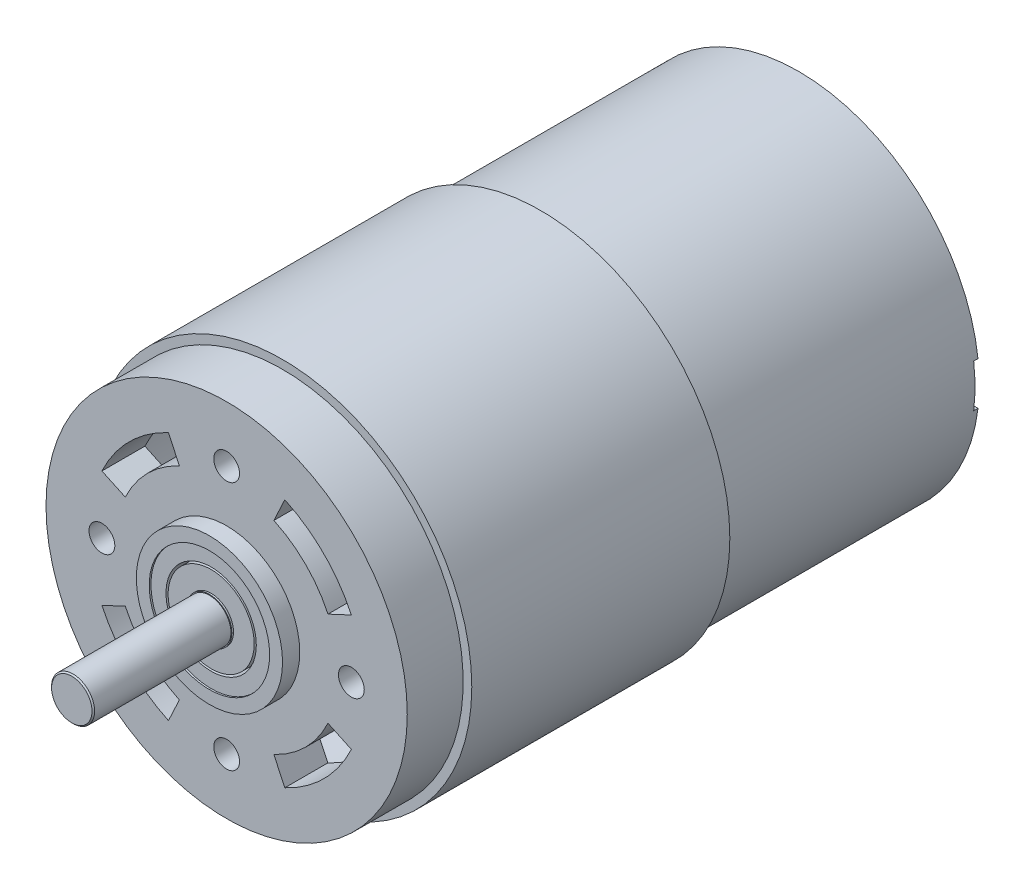
SolidWorks part; units mm, degrees
ref_plane "正面" through (0, 0, 0) normal (0, 0, 1) x (1, 0, 0)
ref_plane "平面" through (0, 0, 0) normal (0, 1, 0) x (1, 0, 0)
ref_plane "右側面" through (0, 0, 0) normal (1, 0, 0) x (0, 0, -1)
sketch "Sketch1" plane through (0, 0, 0) normal (0, 0, 1) x (1, 0, 0)
  circle A0 centre (0, 0) radius 21
  dimension "D1" = 42
extrude "Boss-Extrude1" add sketch "Sketch1" along normal blind 66.5
sketch "Sketch2" plane through (0, 0, 66.5) normal (0, 0, 1) x (1, 0, 0)
  circle A0 centre (0, 0) radius 8.5
  dimension "D1" = 17
extrude "Boss-Extrude2" add sketch "Sketch2" along normal blind 2
sketch "Sketch4" plane through (0, 0, 0) normal (0, 0, -1) x (-1, 0, 0)
  circle A0 centre (0, 0) radius 2.5
  dimension "D1" = 5
extrude "Boss-Extrude3" add sketch "Sketch4" against normal blind 92.5 from offset 8
chamfer "Chamfer1" distance 0.15 angle 45 2 edges at (-2.5, 0, 84.5) (-2.5, 0, -8)
sketch "Sketch5" plane through (0, 0, 66.5) normal (0, 0, 1) x (1, 0, 0)
  line L0 (0, 0) -> (0, 21) construction
  circle A0 centre (0, 0) radius 21 construction
  circle A1 centre (0, 14.5) radius 1.5
  circle A2 centre (14.5, 0) radius 1.5
  circle A3 centre (0, -14.5) radius 1.5
  circle A4 centre (-14.5, 0) radius 1.5
  point P17 (0, 0)
  dimension "D2" = 3
  dimension "D1" = 14.5
  dimension "D3" = 4
extrude "Cut-Extrude1" cut sketch "Sketch5" against normal blind 5
sketch "Sketch7" plane through (0, 0, 0) normal (0, 0, -1) x (-1, 0, 0)
  line L0 (-21, 0) -> (21, 0) construction
  line L1 (0, 21) -> (0, -21) construction
  line L2 (18, -2.5) -> (21, -2.5)
  line L3 (-18, 2.5) -> (-21, 2.5)
  line L4 (-18, 2.5) -> (-18, -2.5)
  line L5 (-18, -2.5) -> (-21, -2.5)
  line L6 (-21, 2.5) -> (-21, -2.5)
  line L7 (-18, 2.5) -> (-21, -2.5) construction
  line L8 (-18, -2.5) -> (-21, 2.5) construction
  line L9 (21, 2.5) -> (21, -2.5)
  line L10 (18, 2.5) -> (21, 2.5)
  line L11 (18, 2.5) -> (18, -2.5)
  circle A0 centre (0, 0) radius 21 construction
  point P7 (-19.5, 0)
  dimension "D1" = 3
  dimension "D2" = 5
extrude "Cut-Extrude2" cut sketch "Sketch7" against normal blind 0.5
sketch "Sketch8" plane through (0, 0, 66.5) normal (0, 0, 1) x (1, 0, 0)
  line L0 (-21, 0) -> (21, 0) construction
  line L1 (-14.8492, -14.8492) -> (14.8492, 14.8492) construction
  line L2 (0, 0) -> (8.875, 19.0325) construction
  line L3 (0, 0) -> (19.0325, 8.875) construction
  line L4 (6.7619, 14.5009) -> (5.494, 11.782)
  line L5 (11.782, 5.494) -> (14.5009, 6.7619)
  line L6 (5.494, -11.782) -> (6.7619, -14.5009)
  line L7 (14.5009, -6.7619) -> (11.782, -5.494)
  line L8 (-11.782, -5.494) -> (-14.5009, -6.7619)
  line L9 (-6.7619, -14.5009) -> (-5.494, -11.782)
  line L10 (-5.494, 11.782) -> (-6.7619, 14.5009)
  line L11 (-14.5009, 6.7619) -> (-11.782, 5.494)
  circle A0 centre (0, 0) radius 13 construction
  circle A1 centre (0, 0) radius 16 construction
  circle A2 centre (0, 0) radius 21 construction
  arc A3 (11.782, 5.494) -> (5.494, 11.782) centre (0, 0) ccw
  arc A4 (14.5009, 6.7619) -> (6.7619, 14.5009) centre (0, 0) ccw
  arc A5 (6.7619, -14.5009) -> (14.5009, -6.7619) centre (0, 0) ccw
  arc A6 (5.494, -11.782) -> (11.782, -5.494) centre (0, 0) ccw
  arc A7 (-14.5009, -6.7619) -> (-6.7619, -14.5009) centre (0, 0) ccw
  arc A8 (-11.782, -5.494) -> (-5.494, -11.782) centre (0, 0) ccw
  arc A9 (-6.7619, 14.5009) -> (-14.5009, 6.7619) centre (0, 0) ccw
  arc A10 (-5.494, 11.782) -> (-11.782, 5.494) centre (0, 0) ccw
  point P10 (0, 0)
  point P32 (0, 0)
  dimension "D1" = 45
  dimension "D2" = 20
  dimension "D3" = 4
extrude "Cut-Extrude3" cut sketch "Sketch8" against normal blind 5
sketch "Sketch9" plane through (0, 0, 0) normal (0, 0, -1) x (-1, 0, 0)
  circle A0 centre (0, 0) radius 22
  dimension "D1" = 44
extrude "Boss-Extrude4" add sketch "Sketch9" against normal blind 30 from offset 30 offset against normal yes
sketch "Sketch10" plane through (0, 0, 0) normal (0, 0, -1) x (-1, 0, 0)
  circle A0 centre (0, 0) radius 20
  circle A1 centre (0, 0) radius 12.5
  dimension "D1" = 40
  dimension "D2" = 25
extrude "Cut-Extrude5" cut sketch "Sketch10" against normal blind 59.5 from offset 2 offset against normal yes
sketch "Sketch12" plane through (0, 0, 0) normal (0, 0, -1) x (-1, 0, 0)
  circle A0 centre (0, 0) radius 5
  circle A1 centre (0, 0) radius 2.6
  dimension "D1" = 10
  dimension "D2" = 5.2
extrude "Boss-Extrude5" add sketch "Sketch12" along normal blind 4
chamfer "Chamfer2" distance 2 angle 45 1 edges at (-5, 0, -4)
sketch "Sketch14" plane through (0, 0, 0) normal (0, 0, -1) x (-1, 0, 0)
  circle A0 centre (0, 0) radius 20
  circle A1 centre (0, 0) radius 14
  dimension "D1" = 40
  dimension "D2" = 28
extrude "Cut-Extrude6" cut sketch "Sketch14" against normal blind 0.3
sketch "Sketch15" plane through (0, 0, 68.5) normal (0, 0, 1) x (1, 0, 0)
  circle A0 centre (0, 0) radius 7
  circle A1 centre (0, 0) radius 2.6
  dimension "D1" = 14
  dimension "D2" = 5.2
extrude "Cut-Extrude7" cut sketch "Sketch15" against normal blind 0.2
sketch "Sketch16" plane through (0, 0, 68.3) normal (0, 0, 1) x (1, 0, 0)
  circle A0 centre (0, 0) radius 5.25
  circle A1 centre (0, 0) radius 5
  dimension "D1" = 10.5
  dimension "D2" = 10
extrude "Cut-Extrude8" cut sketch "Sketch16" against normal blind 5
sketch "Sketch17" plane through (0, 0, 0.3) normal (0, 0, -1) x (-1, 0, 0)
  line L0 (0, 0) -> (15.5563, 15.5563) construction
  line L1 (0, 0) -> (22, 0) construction
  circle A0 centre (0, 0) radius 22 construction
  circle A1 centre (0, 0) radius 17.0015 construction
  circle A2 centre (13.8265, 9.8934) radius 1.25
  circle A3 centre (9.8934, 13.8265) radius 1.25
  circle A4 centre (13.8265, -9.8934) radius 1.25
  circle A5 centre (9.8934, -13.8265) radius 1.25
  circle A6 centre (-9.8934, -13.8265) radius 1.25
  circle A7 centre (-13.8265, -9.8934) radius 1.25
  circle A8 centre (-13.8265, 9.8934) radius 1.25
  circle A9 centre (-9.8934, 13.8265) radius 1.25
  point P27 (0, 0)
  dimension "D2" = 34.0031
  dimension "D3" = 2.5
  dimension "D1" = 45
  dimension "D4" = 4
extrude "Cut-Extrude9" cut sketch "Sketch17" against normal blind 0.3
sketch "Sketch19" plane through (0, 0, 0) normal (0, 0, -1) x (-1, 0, 0)
  line L0 (0, 0) -> (12.5, 0) construction
  line L1 (0, 0) -> (8.8388, 8.8388) construction
  line L2 (0, 0) -> (4.2753, 11.7462) construction
  line L3 (0, 0) -> (11.7462, 4.2753) construction
  line L4 (4.2753, 11.7462) -> (2.9072, 7.9874)
  line L5 (7.9874, 2.9072) -> (11.7462, 4.2753)
  line L6 (2.9072, -7.9874) -> (4.2753, -11.7462)
  line L7 (11.7462, -4.2753) -> (7.9874, -2.9072)
  line L8 (-7.9874, -2.9072) -> (-11.7462, -4.2753)
  line L9 (-4.2753, -11.7462) -> (-2.9072, -7.9874)
  line L10 (-2.9072, 7.9874) -> (-4.2753, 11.7462)
  line L11 (-11.7462, 4.2753) -> (-7.9874, 2.9072)
  circle A0 centre (0, 0) radius 12.5 construction
  circle A1 centre (0, 0) radius 8.5 construction
  arc A2 (11.7462, 4.2753) -> (4.2753, 11.7462) centre (0, 0) ccw
  arc A3 (7.9874, 2.9072) -> (2.9072, 7.9874) centre (0, 0) ccw
  arc A4 (4.2753, -11.7462) -> (11.7462, -4.2753) centre (0, 0) ccw
  arc A5 (2.9072, -7.9874) -> (7.9874, -2.9072) centre (0, 0) ccw
  arc A6 (-11.7462, -4.2753) -> (-4.2753, -11.7462) centre (0, 0) ccw
  arc A7 (-7.9874, -2.9072) -> (-2.9072, -7.9874) centre (0, 0) ccw
  arc A8 (-4.2753, 11.7462) -> (-11.7462, 4.2753) centre (0, 0) ccw
  arc A9 (-2.9072, 7.9874) -> (-7.9874, 2.9072) centre (0, 0) ccw
  point P29 (0, 0)
  dimension "D1" = 25
  dimension "D2" = 17
  dimension "D3" = 45
  dimension "D4" = 25
  dimension "D5" = 4
extrude "Cut-Extrude12" cut sketch "Sketch19" against normal blind 1.5 contours A7 L8 A6 L9 | A3 L5 A2 L4 | A5 L6 A4 L7 | A9 L10 A8 L11 | L6 A4 L7 A5 region at (-7.2782, 7.2782, 0) region at (-7.2782, -7.2782, 0) region at (7.2782, -7.2782, 0) region at (7.2782, 7.2782, 0)
sketch "Sketch20" plane through (0, 0, 0) normal (0, 0, -1) x (-1, 0, 0)
  circle A0 centre (0, 0) radius 20
  circle A1 centre (0, 0) radius 2.5
  dimension "40" = 40
extrude "Cut-Extrude13" cut sketch "Sketch20" against normal blind 1 from offset 1 offset against normal yes
fillet "Fillet1" radius 2 16 edges at (2.9072, -7.9874, 0.5) (4.2753, -11.7462, 0.5) (-4.2753, -11.7462, 0.5) (-11.7462, -4.2753, 0.5) (-2.9072, -7.9874, 0.5) (11.7462, -4.2753, 0.5) (7.9874, -2.9072, 0.5) (-7.9874, -2.9072, 0.5) (-11.7462, 4.2753, 0.5) (-7.9874, 2.9072, 0.5) (7.9874, 2.9072, 0.5) (2.9072, 7.9874, 0.5) (4.2753, 11.7462, 0.5) (11.7462, 4.2753, 0.5) (-2.9072, 7.9874, 0.5) (-4.2753, 11.7462, 0.5)
